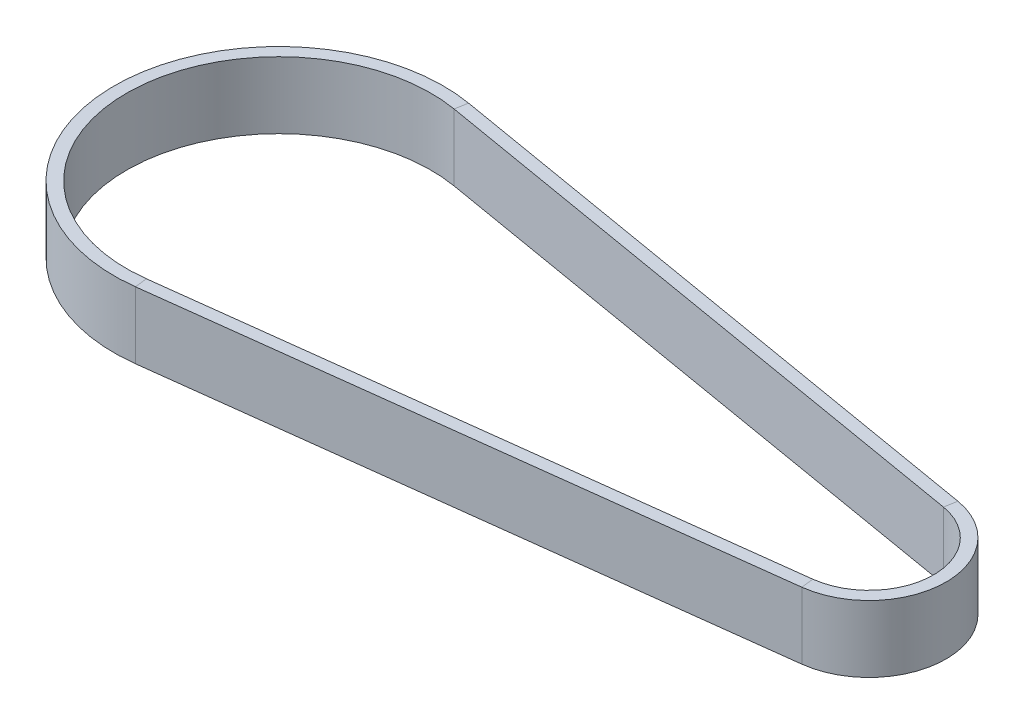
SolidWorks part; units mm, degrees
ref_plane "Front Plane" through (0, 0, 0) normal (0, 0, 1) x (1, 0, 0)
ref_plane "Top Plane" through (0, 0, 0) normal (0, 1, 0) x (1, 0, 0)
ref_plane "Right Plane" through (0, 0, 0) normal (1, 0, 0) x (0, 0, -1)
ref_axis "X" through (-88.99, 0, 0) along (1, 0, 0)
ref_axis "Y" through (0, 0, -88.99) along (0, 0, 1)
ref_axis "Z" through (0, 55, 0) along (0, -1, 0)
sketch "Sketch1" plane through (0, 0, 0) normal (0, 1, 0) x (1, 0, 0)
  line L0 (256.1101, 4211.173) -> (397.5568, 4187.1558)
  line L1 (396.788, 4153.5231) -> (254.3917, 4135.9939)
  arc A0 (256.1101, 4211.173) -> (254.3917, 4135.9939) centre (249.7489, 4173.7092) ccw
  arc A1 (396.788, 4153.5231) -> (397.5568, 4187.1558) centre (394.711, 4170.3957) ccw
  point P13 (394.711, 4170.3957)
  dimension "D1" = 17
  dimension "D2" = 38
ref_plane "Plane1" through (254.3917, 0, -4135.9939) normal (-0.9925, 0, 0.1222) x (0.1222, 0, 0.9925)
sketch "Sketch2" plane through (254.3917, 0, -4135.9939) normal (-0.9925, 0, 0.1222) x (0.1222, 0, 0.9925)
  line L0 (0, 0) -> (-33.2868, 0) construction
  line L1 (-1.5, 8) -> (1.5, 8)
  line L2 (-1.5, 8) -> (-1.5, -8)
  line L3 (-1.5, -8) -> (1.5, -8)
  line L4 (1.5, 8) -> (1.5, -8)
  line L5 (-1.5, 8) -> (1.5, -8) construction
  line L6 (-1.5, -8) -> (1.5, 8) construction
  point P0 (0, 0)
  dimension "D1" = 3
  dimension "D2" = 16
sweep "Sweep1" add profiles "Sketch2" path "Sketch1"
